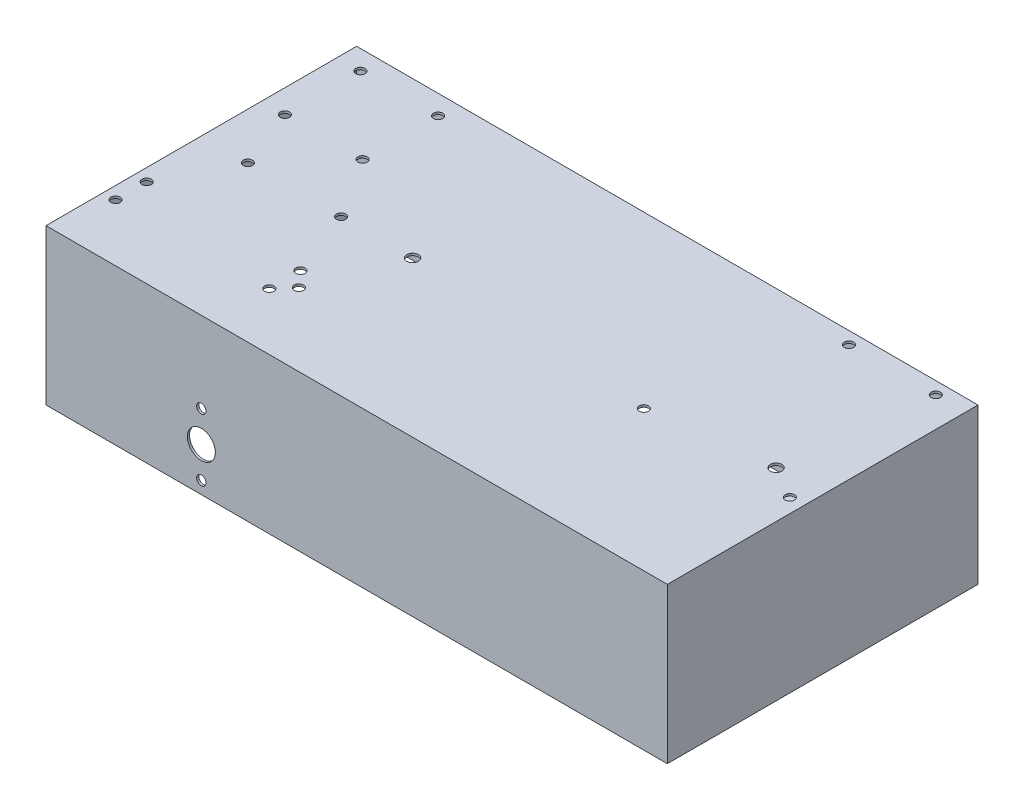
SolidWorks part; units mm, degrees
ref_plane "Front Plane" through (0, 0, 0) normal (0, 0, 1) x (1, 0, 0)
ref_plane "Top Plane" through (0, 0, 0) normal (0, 1, 0) x (1, 0, 0)
ref_plane "Right Plane" through (0, 0, 0) normal (1, 0, 0) x (0, 0, -1)
sketch "Sketch1" plane through (0, 0, 0) normal (0, 1, 0) x (1, 0, 0)
  line L1 (0, 50) -> (200, 50)
  line L2 (0, 50) -> (0, -50)
  line L3 (0, -50) -> (200, -50)
  line L4 (200, 50) -> (200, -50)
  point P4 (0, 0)
  dimension "D1" = 200
  dimension "D2" = 100
extrude "Boss-Extrude1" add sketch "Sketch1" along normal blind 50
sketch "Sketch2" plane through (0, 0, 50) normal (0, 0, 1) x (1, 0, 0)
  line L0 (0, 50) -> (0, 0) construction
  line L1 (50, 24) -> (50, 4) construction
  line L2 (0, 50) -> (200, 50) construction
  circle A0 centre (50, 14) radius 4.5
  circle A1 centre (50, 4) radius 1.5
  circle A2 centre (50, 24) radius 1.5
  point P0 (50, 14)
  point P9 (50, 14)
  dimension "D3" = 9
  dimension "D4" = 3
  dimension "D1" = 50
  dimension "D2" = 36
  dimension "D5" = 20
sketch "Sketch3" plane through (0, 0, 0) normal (0, -1, 0) x (1, 0, 0)
  line L0 (0.7, 49.3) -> (0.7, -49.3)
  line L1 (0.7, -49.3) -> (199.3, -49.3)
  line L2 (199.3, -49.3) -> (199.3, 49.3)
  line L3 (199.3, 49.3) -> (0.7, 49.3)
  line L4 (0, 50) -> (0, -50)
  line L5 (0, -50) -> (200, -50)
  line L6 (200, -50) -> (200, 50)
  line L7 (200, 50) -> (0, 50)
  line L8 (0, 50) -> (0, -50) construction
  line L9 (0, -50) -> (200, -50) construction
  line L10 (200, -50) -> (200, 50) construction
  line L11 (200, 50) -> (0, 50) construction
  dimension "D1" = 0
  dimension "D2" = 0.7
extrude "Cut-Extrude1" cut sketch "Sketch3" against normal offset from surface (49.3 mm away) 0.7 up to face at (100, 50, 0)
sketch "Sketch4" plane through (0, 0, 0) normal (0, -1, 0) x (1, 0, 0)
  line L0 (0.7, -49.3) -> (199.3, -49.3) construction
  line L1 (145, -49.3) -> (199.3, -49.3)
  line L2 (145, -49.3) -> (145, 49.3)
  line L3 (145, 49.3) -> (199.3, 49.3)
  line L4 (199.3, -49.3) -> (199.3, 49.3)
  line L5 (199.3, 49.3) -> (0.7, 49.3) construction
  line L6 (160, -47.9) -> (160, 49.3) construction
  line L7 (200, -50) -> (200, 50) construction
  line L8 (199.3, -49.3) -> (199.3, 49.3) construction
  circle A0 centre (160, 0.7) radius 11.43 construction
  point P12 (160, 0.7)
  dimension "D3" = 22.86
  dimension "D1" = 40
  dimension "D2" = 55
  dimension "D4" = 50
extrude "Boss-Extrude2" add sketch "Sketch4" against normal blind 0.7
extrude "Cut-Extrude2" cut sketch "Sketch2" against normal through all
sketch "Sketch8" plane through (0, 0, 0) normal (0, -1, 0) x (1, 0, 0)
  line L0 (160, -47.9) -> (160, 49.3) construction
  circle A0 centre (160, 8.45) radius 1.21
  circle A1 centre (160, -7.05) radius 1.21
  dimension "D2" = 2.42
  dimension "D1" = 7.75
  dimension "D3" = 7.75
extrude "Cut-Extrude6" cut sketch "Sketch8" against normal blind 1.8 contours A1 | A0
sketch "Sketch9" plane through (0, 50, 0) normal (0, 1, 0) x (1, 0, 0)
  line L0 (0, 0) -> (200, 0) construction
  line L1 (200, 50) -> (200, -50) construction
  line L2 (0, 50) -> (200, 50) construction
  line L5 (7.5, 43.7) -> (32.5, 43.7) construction
  line L6 (7.5, 43.7) -> (7.5, 19.4) construction
  line L7 (7.5, 19.4) -> (32.5, 19.4) construction
  line L8 (32.5, 43.7) -> (32.5, 19.4) construction
  line L9 (0, -50) -> (0, 50) construction
  circle A0 centre (15, 0) radius 1.5
  circle A1 centre (45, 0) radius 1.5
  circle A2 centre (7.5, 43.7) radius 1.5
  circle A3 centre (7.5, 19.4) radius 1.5
  circle A4 centre (32.5, 43.7) radius 1.5
  circle A5 centre (32.5, 19.4) radius 1.5
  dimension "D1" = 3
  dimension "D4" = 25
  dimension "D8" = 3
  dimension "D2" = 15
  dimension "D3" = 30
  dimension "D5" = 24.3
  dimension "D6" = 6.3
  dimension "D7" = 7.5
sketch "Sketch10" plane through (0, 49.3, 0) normal (0, -1, 0) x (1, 0, 0)
  line L0 (0, 0) -> (200, 0)
  line L1 (200, -50) -> (200, 50) construction
  circle A0 centre (185, 0) radius 1.87
  circle A1 centre (68, 0) radius 1.87
  dimension "D2" = 3.74
  dimension "D1" = 117
  dimension "D3" = 15
extrude "Cut-Extrude8" cut sketch "Sketch10" against normal up to surface (0.7 mm away) contours A0 | A1 up to face at (100, 50, 0)
extrude "Cut-Extrude7" cut sketch "Sketch9" against normal up to next
sketch "Sketch11" plane through (143.38, 50, -175.08) normal (0, 1, 0) x (0, 0, 1)
  line L6 (129.04, 19.06) -> (129.04, 47) construction
  circle A0 centre (129.04, 47) radius 1.5
  circle A1 centre (181.11, 52.08) radius 1.5
  circle A2 centre (179.84, 3.82) radius 1.5
  circle A3 centre (129.04, 19.06) radius 1.5
  point P12 (195.08, 54.62)
  dimension "D8" = 3
  dimension "D1" = 13.97
  dimension "D2" = 66.04
  dimension "D3" = 15.24
  dimension "D4" = 2.54
  dimension "D5" = 7.62
  dimension "D6" = 50.8
  dimension "D7" = 35.56
  dimension "D9" = 70
  dimension "D10" = 2
extrude "Cut-Extrude9" cut sketch "Sketch11" against normal up to surface (0.7 mm away) up to face at (7.5, 49.3, -17.9)
sketch "Sketch12" plane through (0, 50, 0) normal (0, 1, 0) x (1, 0, 0)
  line L0 (58, -26.6) -> (53.5, -26.6) construction
  line L1 (4, -21.6) -> (53.5, -21.6) construction
  line L2 (4, -21.6) -> (4, -31.6) construction
  line L3 (4, -31.6) -> (53.5, -31.6) construction
  line L4 (53.5, -21.6) -> (53.5, -31.6) construction
  line L5 (200, -50) -> (0, -50) construction
  line L6 (0, -50) -> (0, 50) construction
  circle A0 centre (4, -21.6) radius 1.5
  circle A1 centre (53.5, -21.6) radius 1.5
  circle A2 centre (53.5, -31.6) radius 1.5
  circle A3 centre (4, -31.6) radius 1.5
  circle A4 centre (58, -26.6) radius 1.5
  point P10 (53.5, -26.6)
  dimension "D2" = 3
  dimension "D1" = 4.5
  dimension "D3" = 49.5
  dimension "D4" = 10
  dimension "D5" = 18.4
  dimension "D6" = 4
extrude "Cut-Extrude10" cut sketch "Sketch12" against normal up to next
